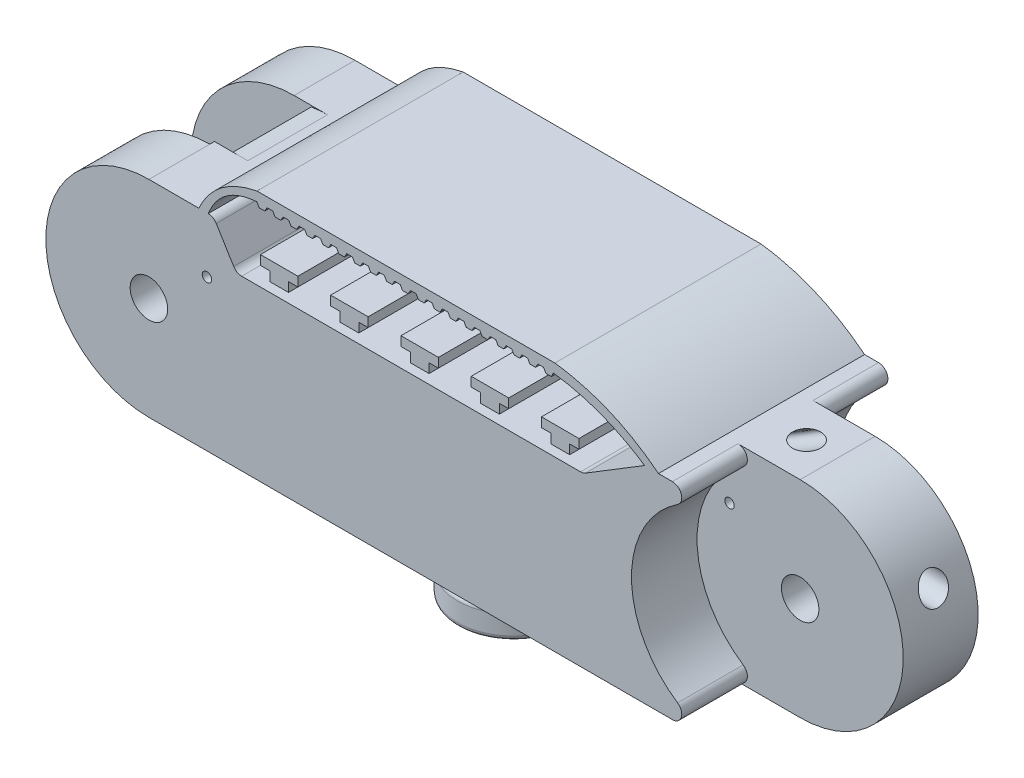
SolidWorks part; units mm, degrees
ref_plane "Front Plane" through (0, 0, 0) normal (0, 0, 1) x (1, 0, 0)
ref_plane "Top Plane" through (0, 0, 0) normal (0, 1, 0) x (1, 0, 0)
ref_plane "Right Plane" through (0, 0, 0) normal (1, 0, 0) x (0, 0, -1)
sketch "Sketch1" plane through (0, 0, 0) normal (0, 0, 1) x (1, 0, 0)
  line L0 (-32.5849, 24.9928) -> (29.9151, 24.9928)
  line L1 (-32.5849, 2.9928) -> (-23.0933, 2.9928)
  line L3 (18.774, 2.9928) -> (-23.0933, 2.9928)
  line L10 (18.774, 2.9928) -> (29.9151, 2.9928)
  arc A0 (29.9151, 2.9928) -> (29.9151, 24.9928) centre (29.9151, 13.9928) ccw
  arc A1 (-32.5849, 24.9928) -> (-32.5849, 2.9928) centre (-32.5849, 13.9928) ccw
  dimension "D1" = 22
  dimension "D2" = 62.5
extrude "Gripper Body" add sketch "Sketch1" along normal mid plane 22
sketch "Sketch3" plane through (0, 0, 0) normal (0, 0, 1) x (1, 0, 0)
  line L0 (-32.5849, 13.9928) -> (-32.5849, 24.9928) construction
  line L1 (29.9151, 24.9928) -> (-32.5849, 24.9928) construction
  arc A0 (-32.5849, 24.9928) -> (-32.5849, 2.9928) centre (-32.5849, 13.9928) ccw construction
  circle A1 centre (-32.5849, 13.9928) radius 11
extrude "Connection to Gripper 1" cut sketch "Sketch3" against normal mid plane 9
sketch "Sketch6" plane through (0, 0, 11) normal (0, 0, 1) x (1, 0, 0)
  line L0 (29.9151, 13.9928) -> (29.9151, 24.9928) construction
  circle A0 centre (29.9151, 13.9928) radius 11
extrude "Cut-Extrude8" cut sketch "Sketch6" against normal blind 7
sketch "Sketch7" plane through (0, 0, -11) normal (0, 0, -1) x (-1, 0, 0)
  line L0 (-29.9151, 13.9928) -> (-29.9151, 24.9928) construction
  circle A0 centre (-29.9151, 13.9928) radius 11
extrude "Cut-Extrude9" cut sketch "Sketch7" against normal blind 7
fillet "Fillet4" radius 1 2 edges at (29.9151, 24.9928, -7.5) (29.9151, 24.9928, 7.5)
fillet "Fillet5" radius 1 2 edges at (29.9151, 2.9928, 7.5) (29.9151, 2.9928, -7.5)
sketch "Sketch9" plane through (0, 0, -4) normal (0, 0, -1) x (-1, 0, 0)
  line L0 (-29.9151, 13.9928) -> (-29.9151, 2.9928) construction
  circle A0 centre (-29.9151, 13.9928) radius 2
  dimension "D1" = 4
extrude "Joint Hole 1" cut sketch "Sketch9" against normal blind 8
sketch "Sketch10" plane through (0, 0, -11) normal (0, 0, -1) x (-1, 0, 0)
  line L0 (32.5849, 13.9928) -> (32.5849, 24.9928) construction
  circle A0 centre (32.5849, 13.9928) radius 2
  dimension "D1" = 4
extrude "Joint Holes 2" cut sketch "Sketch10" against normal through all both and the other way through all
sketch "Sketch11" plane through (0, 0, -11) normal (0, 0, -1) x (-1, 0, 0)
  line L1 (-23.2819, 24.9928) -> (32.5849, 24.9928) construction
  line L2 (-20.3089, 24.9928) -> (25.6911, 24.9928)
  line L4 (32.5849, 13.9928) -> (32.5849, 18.0137) construction
  line L5 (-20.3089, 24.9928) -> (-14.0018, 21.1395)
  line L7 (25.6911, 24.9928) -> (23.5397, 21.4715)
  line L8 (-13.4805, 20.9928) -> (22.6863, 20.9928)
  arc A0 (-14.0018, 21.1395) -> (-13.4805, 20.9928) centre (-13.4805, 21.9928) ccw
  arc A1 (23.5397, 21.4715) -> (22.6863, 20.9928) centre (22.6863, 21.9928) cw
  dimension "D1" = 1
  dimension "D2" = 1
  dimension "D3" = 4
  dimension "D4" = 46
extrude "Silicon Depression" cut sketch "Sketch11" against normal blind 22
sketch "Sketch12" plane through (0, 20.9928, 0) normal (0, 1, 0) x (1, 0, 0)
  line L1 (-20.6863, 10) -> (-18.6863, 10)
  line L2 (-20.6863, 10) -> (-20.6863, -10)
  line L3 (-20.6863, -10) -> (-18.6863, -10)
  line L4 (-18.6863, 10) -> (-18.6863, -10)
  line L6 (13.4805, -11) -> (-22.6863, -11) construction
  line L8 (-22.6863, -11) -> (-22.6863, 11) construction
  line L10 (-20.6863, 0) -> (-18.6863, 0) construction
  line L11 (-18.6863, 0) -> (-19.6863, 0) construction
  line L12 (-19.6863, 0) -> (-19.6863, 2.3263) construction
  line L13 (-12.51, 0) -> (-26.8627, 0) construction
  line L14 (-19.6863, 0) -> (-19.6863, 1.7285) construction
  dimension "D1" = 1
  dimension "D2" = 2
  dimension "D3" = 2
extrude "Silicon Holder Bottom Half" add sketch "Sketch12" along normal blind 1
sketch "Sketch13" plane through (0, 21.9928, 0) normal (0, 1, 0) x (1, 0, 0)
  line L0 (-21.6863, 10) -> (-17.6863, 10)
  line L1 (-21.6863, 10) -> (-21.6863, -10)
  line L2 (-21.6863, -10) -> (-17.6863, -10)
  line L3 (-17.6863, 10) -> (-17.6863, -10)
  line L4 (-20.6863, 0) -> (-18.6863, 0) construction
  line L5 (-20.6863, 10) -> (-20.6863, -10) construction
  line L6 (-18.6863, -10) -> (-18.6863, 10) construction
  line L7 (-19.6863, 0) -> (-19.6863, 1) construction
  line L8 (-21.6863, 0) -> (-17.6863, 0) construction
  line L9 (-19.6863, 0) -> (-19.6863, 1.9805) construction
  dimension "D1" = 4
  dimension "D2" = 20
extrude "Silicon Holder Top Half" add sketch "Sketch13" along normal blind 1
pattern_linear "Silicon Holders" count 5 spacing 7.5 along (1, 0, 0) of "Silicon Holder Top Half", "Silicon Holder Bottom Half"
sketch "Sketch16" plane through (0, 0, -11) normal (0, 0, -1) x (-1, 0, 0)
  circle A7 centre (-22.3786, 19.0588) radius 0.5
  circle A10 centre (26.3933, 19.0588) radius 0.5
extrude "Tendon Routing Pins" cut sketch "Sketch16" against normal through all
sketch "Sketch20" plane through (0, 0, 0) normal (1, 0, 0) x (0, 0, -1)
  line L0 (0, 18.5588) -> (0, 19.0588) construction
  line L1 (0, 18.0088) -> (0, 19.5088) construction
  circle A0 centre (0, 18.0088) radius 1.5
  dimension "D1" = 3
  dimension "D2" = 0.55
extrude "Tendon Hole" cut sketch "Sketch20" against normal through all both and the other way through all
sketch "Sketch21" plane through (0, 2.9928, 0) normal (0, -1, 0) x (1, 0, 0)
  line L0 (-32.5849, -11) -> (23.2819, -11) construction
  line L3 (-4.6515, -11) -> (-4.6515, 11) construction
  line L4 (-32.5849, 11) -> (23.2819, 11) construction
  circle A0 centre (-4.6515, 0) radius 4
extrude "Elastic Band Holder 1st Half" add sketch "Sketch21" along normal blind 5
sketch "Sketch22" plane through (0, -2.0072, 0) normal (0, -1, 0) x (1, 0, 0)
  line L0 (-4.6515, 0) -> (-4.6515, -4) construction
  circle A0 centre (-4.6515, 0) radius 4 construction
  circle A1 centre (-4.6515, 0) radius 6
extrude "Elastic Band Holder 2nd Half" add sketch "Sketch22" along normal blind 3
fillet "Fillet9" radius 0.5 3 edges at (1.3485, -5.0072, 0) (1.3485, -2.0072, 0) (-0.6515, -2.0072, 0)
sketch "Sketch26" plane through (0, 24.9928, 0) normal (0, 1, 0) x (1, 0, 0)
  line L1 (-32.5849, 4.5) -> (-30.7615, 4.5)
  line L2 (-32.5849, 4.5) -> (-32.5849, -4.0007)
  line L3 (-32.5849, -4.0007) -> (-30.7615, -4.0007)
  line L4 (-30.7615, 4.5) -> (-30.7615, -4.0007)
extrude "Cut-Extrude12" cut sketch "Sketch26" against normal blind 10
fillet "Fillet10" radius 10 1 edges at (-30.7615, 24.9928, -0.2497)
fillet "Fillet15" radius 1 1 edges at (-25.6911, 24.9928, 0)
sketch "Sketch27" plane through (0, 0, 11) normal (0, 0, 1) x (1, 0, 0)
  line L1 (-21.0671, 28.6834) -> (-20.8171, 28.2504)
  line L2 (-18.2671, 28.6834) -> (-17.6671, 28.6834)
  line L3 (-21.051, 29.6832) -> (10.7422, 29.6832)
  line L4 (-20.8171, 28.2504) -> (-20.2171, 28.2504)
  line L5 (-20.2171, 28.2504) -> (-19.9671, 28.6834)
  line L6 (-19.9671, 28.6834) -> (-19.3671, 28.6834)
  line L7 (-19.1171, 28.2504) -> (-19.3671, 28.6834)
  line L8 (-18.5171, 28.2504) -> (-19.1171, 28.2504)
  line L9 (-18.2671, 28.6834) -> (-18.5171, 28.2504)
  line L10 (-17.4171, 28.2504) -> (-17.6671, 28.6834)
  line L11 (-16.8171, 28.2504) -> (-17.4171, 28.2504)
  line L12 (-16.5671, 28.6834) -> (-16.8171, 28.2504)
  line L13 (-14.8671, 28.6834) -> (-14.2671, 28.6834)
  line L14 (-16.5671, 28.6834) -> (-15.9671, 28.6834)
  line L15 (-15.7171, 28.2504) -> (-15.9671, 28.6834)
  line L16 (-15.1171, 28.2504) -> (-15.7171, 28.2504)
  line L17 (-14.8671, 28.6834) -> (-15.1171, 28.2504)
  line L18 (-14.0171, 28.2504) -> (-14.2671, 28.6834)
  line L19 (-13.4171, 28.2504) -> (-14.0171, 28.2504)
  line L20 (-13.1671, 28.6834) -> (-13.4171, 28.2504)
  line L21 (-11.4671, 28.6834) -> (-10.8671, 28.6834)
  line L22 (-13.1671, 28.6834) -> (-12.5671, 28.6834)
  line L23 (-12.3171, 28.2504) -> (-12.5671, 28.6834)
  line L24 (-11.7171, 28.2504) -> (-12.3171, 28.2504)
  line L25 (-11.4671, 28.6834) -> (-11.7171, 28.2504)
  line L26 (-10.6171, 28.2504) -> (-10.8671, 28.6834)
  line L27 (-10.0171, 28.2504) -> (-10.6171, 28.2504)
  line L28 (-9.7671, 28.6834) -> (-10.0171, 28.2504)
  line L29 (-8.0671, 28.6834) -> (-7.4671, 28.6834)
  line L30 (-9.7671, 28.6834) -> (-9.1671, 28.6834)
  line L31 (-8.9171, 28.2504) -> (-9.1671, 28.6834)
  line L32 (-8.3171, 28.2504) -> (-8.9171, 28.2504)
  line L33 (-8.0671, 28.6834) -> (-8.3171, 28.2504)
  line L34 (-7.2171, 28.2504) -> (-7.4671, 28.6834)
  line L35 (-6.6171, 28.2504) -> (-7.2171, 28.2504)
  line L36 (-6.3671, 28.6834) -> (-6.6171, 28.2504)
  line L37 (-4.6671, 28.6834) -> (-4.0671, 28.6834)
  line L38 (-6.3671, 28.6834) -> (-5.7671, 28.6834)
  line L39 (-5.5171, 28.2504) -> (-5.7671, 28.6834)
  line L40 (-4.9171, 28.2504) -> (-5.5171, 28.2504)
  line L41 (-4.6671, 28.6834) -> (-4.9171, 28.2504)
  line L42 (-3.8171, 28.2504) -> (-4.0671, 28.6834)
  line L43 (-3.2171, 28.2504) -> (-3.8171, 28.2504)
  line L44 (-2.9671, 28.6834) -> (-3.2171, 28.2504)
  line L45 (-1.2671, 28.6834) -> (-0.6671, 28.6834)
  line L46 (-2.9671, 28.6834) -> (-2.3671, 28.6834)
  line L47 (-2.1171, 28.2504) -> (-2.3671, 28.6834)
  line L48 (-1.5171, 28.2504) -> (-2.1171, 28.2504)
  line L49 (-1.2671, 28.6834) -> (-1.5171, 28.2504)
  line L50 (-0.4171, 28.2504) -> (-0.6671, 28.6834)
  line L51 (0.1829, 28.2504) -> (-0.4171, 28.2504)
  line L52 (0.4329, 28.6834) -> (0.1829, 28.2504)
  line L53 (2.1329, 28.6834) -> (2.7329, 28.6834)
  line L54 (0.4329, 28.6834) -> (1.0329, 28.6834)
  line L55 (1.2829, 28.2504) -> (1.0329, 28.6834)
  line L56 (1.8829, 28.2504) -> (1.2829, 28.2504)
  line L57 (2.1329, 28.6834) -> (1.8829, 28.2504)
  line L58 (2.9829, 28.2504) -> (2.7329, 28.6834)
  line L59 (3.5829, 28.2504) -> (2.9829, 28.2504)
  line L60 (3.8329, 28.6834) -> (3.5829, 28.2504)
  line L61 (5.5329, 28.6834) -> (6.1329, 28.6834)
  line L62 (3.8329, 28.6834) -> (4.4329, 28.6834)
  line L63 (4.6829, 28.2504) -> (4.4329, 28.6834)
  line L64 (5.2829, 28.2504) -> (4.6829, 28.2504)
  line L65 (5.5329, 28.6834) -> (5.2829, 28.2504)
  line L66 (6.3829, 28.2504) -> (6.1329, 28.6834)
  line L67 (6.9829, 28.2504) -> (6.3829, 28.2504)
  line L68 (7.2329, 28.6834) -> (6.9829, 28.2504)
  line L69 (8.9329, 28.6834) -> (9.5329, 28.6834)
  line L70 (7.2329, 28.6834) -> (7.8329, 28.6834)
  line L71 (8.0829, 28.2504) -> (7.8329, 28.6834)
  line L72 (8.6829, 28.2504) -> (8.0829, 28.2504)
  line L73 (8.9329, 28.6834) -> (8.6829, 28.2504)
  line L74 (9.7829, 28.2504) -> (9.5329, 28.6834)
  line L75 (10.3829, 28.2504) -> (9.7829, 28.2504)
  line L76 (10.5693, 28.6834) -> (10.3829, 28.2504)
  line L79 (10.3137, 22.9928) -> (10.3137, 27.9928) construction
  line L80 (8.3137, 22.9928) -> (12.3137, 22.9928) construction
  line L81 (-26.252, 24.9928) -> (-27.252, 24.9928)
  line L82 (-26.252, 24.9928) -> (-32.5849, 24.9928) construction
  line L83 (20.3089, 24.9928) -> (21.7954, 24.9928)
  line L84 (23.2819, 24.9928) -> (20.3089, 24.9928) construction
  spline S0 degree 2 poles (-26.252, 24.9928) (-24.9316, 28.374) (-21.0671, 28.6834) knots 0 0 0 1 1 1
  spline S1 degree 2 poles (-27.252, 24.9928) (-25.5122, 28.8236) (-21.051, 29.6832) knots 0 0 0 1 1 1
  spline S2 degree 2 poles (20.3089, 24.9928) (15.9002, 27.9936) (10.5693, 28.6834) knots 0 0 0 1 1 1
  spline S3 degree 2 poles (21.7954, 24.9928) (16.9353, 28.8712) (10.7422, 29.6832) knots 0 0 0 1 1 1
  dimension "D1" = 1
  dimension "D2" = 1
extrude "Boss-Extrude1" add sketch "Sketch27" against normal blind 22
sketch "Sketch29" plane through (0, 24.9928, 0) normal (0, 1, 0) x (1, 0, 0)
  line L0 (23.2819, 4) -> (26.5985, 4) construction
  line L1 (29.9151, 4) -> (23.2819, 4) construction
  line L2 (26.5985, 4) -> (26.5985, -4) construction
  line L3 (23.2819, -4) -> (29.9151, -4) construction
  line L4 (26.5985, -4) -> (26.5985, 0) construction
  line L5 (26.5985, 0) -> (28.0452, 0) construction
  circle A0 centre (26.5985, 0) radius 1.5
  dimension "D1" = 3
extrude "Cut-Extrude13" cut sketch "Sketch29" along direction (-0.8533, -0.5214, 0) on the side against the normal blind 14
